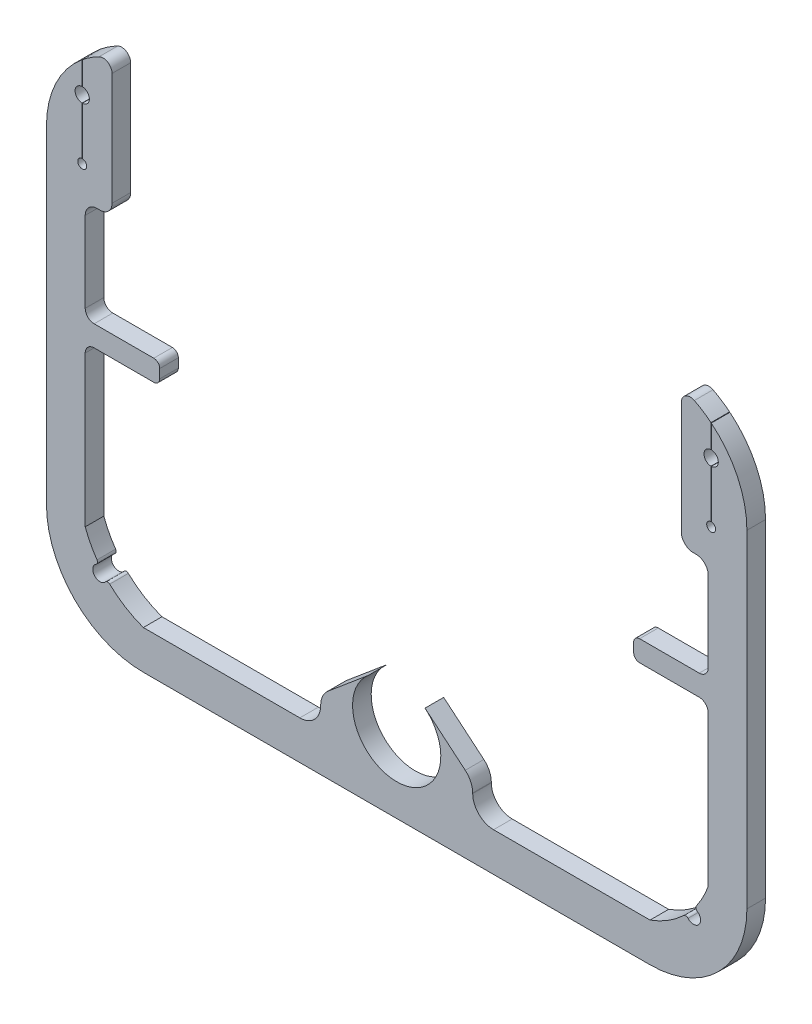
SolidWorks part; units mm, degrees
material "Delrin 2700 NC010, Low Viscosity Acetal Copolymer (SS)"
ref_plane "Front Plane" through (0, 0, 0) normal (0, 0, 1) x (1, 0, 0)
ref_plane "Top Plane" through (0, 0, 0) normal (0, 1, 0) x (1, 0, 0)
ref_plane "Right Plane" through (0, 0, 0) normal (1, 0, 0) x (0, 0, -1)
sketch "Sketch1" plane through (0, 0, 0) normal (0, 0, 1) x (1, 0, 0)
  line L0 (-21.59, -18.923) -> (-9.6321, -18.923)
  line L1 (21.59, 22.225) -> (-21.59, 22.225)
  line L2 (29.845, 13.97) -> (29.845, -13.97)
  line L3 (21.59, -22.225) -> (-21.59, -22.225)
  line L4 (-29.845, 13.97) -> (-29.845, -13.97)
  line L5 (29.845, 22.225) -> (-29.845, -22.225) construction
  line L6 (29.845, -22.225) -> (-29.845, 22.225) construction
  line L7 (9.6321, -18.923) -> (21.59, -18.923)
  line L8 (-26.543, -0.381) -> (-20.193, -0.381)
  line L9 (26.543, 1.397) -> (20.193, 1.397)
  line L10 (-26.543, 10.033) -> (-26.543, -13.97)
  line L11 (-1000, 0) -> (49000, 0) construction
  line L12 (-26.543, 0) -> (-26.543, -1.27)
  line L13 (26.543, 10.033) -> (26.543, -13.97)
  line L14 (21.59, 18.923) -> (-21.59, 18.923)
  line L15 (26.543, 1.397) -> (26.543, -0.381)
  line L16 (26.543, -0.381) -> (20.193, -0.381)
  line L17 (20.193, 1.397) -> (20.193, -0.381)
  line L18 (0, 18.923) -> (0, -18.415) construction
  line L19 (-20.193, 1.397) -> (-20.193, -0.381)
  line L20 (-26.543, 1.397) -> (-20.193, 1.397)
  line L21 (2.4164, -12.8683) -> (9.6321, -18.923)
  line L22 (-2.4164, -12.8683) -> (-9.6321, -18.923)
  line L23 (21.59, 18.923) -> (21.59, 10.033)
  line L24 (-21.59, 18.923) -> (-21.59, 10.033)
  line L26 (-21.59, 10.033) -> (-26.543, 10.033)
  line L28 (21.59, 10.033) -> (26.543, 10.033)
  line L29 (-26.543, 13.97) -> (-26.543, -13.97) construction
  line L31 (26.543, 13.97) -> (26.543, -13.97) construction
  line L36 (21.59, -18.923) -> (-21.59, -18.923) construction
  arc A0 (-2.4164, -12.8683) -> (2.4164, -12.8683) centre (0, -15.748) ccw
  arc A1 (-21.59, 22.225) -> (-29.845, 13.97) centre (-21.59, 13.97) ccw
  arc A2 (21.59, 22.225) -> (29.845, 13.97) centre (21.59, 13.97) cw
  arc A3 (29.845, -13.97) -> (21.59, -22.225) centre (21.59, -13.97) cw
  arc A4 (-21.59, -22.225) -> (-29.845, -13.97) centre (-21.59, -13.97) cw
  arc A5 (-26.543, -13.97) -> (-21.59, -18.923) centre (-18.7807, -11.1607) ccw
  arc A6 (26.543, -13.97) -> (21.59, -18.923) centre (18.7807, -11.1607) cw
  arc A13 (-21.59, -18.923) -> (-26.543, -13.97) centre (-21.59, -13.97) cw construction
  arc A14 (26.543, -13.97) -> (21.59, -18.923) centre (21.59, -13.97) cw construction
  arc A17 (21.59, 18.923) -> (26.543, 13.97) centre (21.59, 13.97) cw construction
  arc A18 (-21.59, 18.923) -> (-26.543, 13.97) centre (-21.59, 13.97) ccw construction
  point P0 (0, 0)
  dimension "D4" = 7.5184
  dimension "D6" = 8.255
  dimension "D7" = 8.255
  dimension "D8" = 8.255
  dimension "D9" = 8.255
  dimension "D5" = 8.89
  dimension "D1" = 59.69
  dimension "D2" = 44.45
  dimension "D10" = 3.302
  dimension "D3" = 3.175
  dimension "D13" = 15.748
  dimension "D14" = 1.778
  dimension "D15" = 21.844
  dimension "D16" = 6.35
extrude "Boss-Extrude1" add sketch "Sketch1" along normal blind 1.5875 contours A4 L3 A3 L2 A2 L1 A1 L4 A6 L7 L21 A0 L22 L0 A5 L10 L14 L13 | L9 L17 L16 L13 | L20 L10 L8 L19 region at (-23.368, 0.508, 0) region at (23.368, 0.508, 0) region at (26.9009, 19.2809, 0)
sketch "Sketch2" plane through (0, 0, 1.5875) normal (0, 0, 1) x (1, 0, 0)
  line L0 (-21.59, 10.033) -> (-26.543, 10.033) construction
  line L1 (-9.6321, -18.923) -> (-6.477, -18.923)
  line L2 (-9.6321, -18.923) -> (-9.6321, -16.2756)
  line L3 (-9.6321, -16.2756) -> (-6.477, -16.2756)
  line L4 (-6.477, -18.923) -> (-6.477, -16.2756)
  line L5 (0, -1000) -> (0, 49000) construction
  line L6 (9.6321, -18.923) -> (9.6321, -16.2756)
  line L7 (9.6321, -16.2756) -> (6.477, -16.2756)
  line L8 (6.477, -18.923) -> (6.477, -16.2756)
  line L9 (9.6321, -18.923) -> (6.477, -18.923)
  line L10 (-29.845, 13.97) -> (-29.845, -13.97) construction
  line L11 (-21.59, 18.923) -> (21.59, 18.923)
  line L12 (-24.257, 10.033) -> (-24.257, 22.225)
  line L13 (-24.257, 22.225) -> (24.257, 22.225)
  line L14 (24.257, 10.033) -> (24.257, 22.225)
  line L16 (21.59, 18.923) -> (-21.59, 18.923) construction
  line L17 (-2.4164, -12.8683) -> (-9.6321, -18.923) construction
  line L18 (21.59, 22.225) -> (-21.59, 22.225) construction
  line L19 (21.59, 18.923) -> (-21.59, 18.923) construction
  line L22 (-21.59, 18.923) -> (-21.59, 10.033) construction
  line L23 (21.59, 10.033) -> (26.543, 10.033) construction
  line L24 (21.59, 18.923) -> (21.59, 10.033) construction
  line L25 (-21.59, 18.923) -> (-21.59, 10.033)
  line L26 (-21.59, 10.033) -> (-24.257, 10.033)
  line L27 (21.59, 10.033) -> (24.257, 10.033)
  line L28 (21.59, 18.923) -> (21.59, 10.033)
  point P25 (0, 22.225)
  dimension "D1" = 6.477
  dimension "D2" = 5.588
extrude "Cut-Extrude1" cut sketch "Sketch2" against normal up to next
fillet "Fillet1" radius 1.778 4 edges at (6.477, -18.923, 0.7937) (6.477, -16.2756, 0.7937) (-6.477, -18.923, 0.7937) (-6.477, -16.2756, 0.7937)
fillet "Fillet2" radius 0.762 2 edges at (24.257, 21.7823, 0.7937) (-24.257, 21.7823, 0.7937)
fillet "Fillet3" radius 0.762 4 edges at (-26.543, -0.381, 0.7937) (26.543, -0.381, 0.7937) (26.543, 1.397, 0.7937) (-26.543, 1.397, 0.7937)
sketch "Sketch3" plane through (0, 0, 1.5875) normal (0, 0, 1) x (1, 0, 0)
  line L0 (-25.019, -16.51) -> (-25.2884, -16.7794) construction
  line L1 (21.59, -22.225) -> (-21.59, -22.225) construction
  line L3 (25.2884, -16.7794) -> (25.019, -16.51) construction
  circle A0 centre (-25.019, -16.51) radius 0.6096 construction
  circle A1 centre (-25.019, 16.256) radius 0.6096 construction
  circle A2 centre (25.019, 16.256) radius 0.6096 construction
  circle A3 centre (25.019, -16.51) radius 0.6096 construction
  circle A4 centre (-25.019, -16.51) radius 0.6096 construction
  circle A5 centre (-25.019, 16.256) radius 0.6096 construction
  circle A6 centre (25.019, 16.256) radius 0.6096 construction
  circle A7 centre (25.019, -16.51) radius 0.6096 construction
  circle A8 centre (-26.797, 17.78) radius 0.6096
  circle A9 centre (-25.2884, -16.7794) radius 0.6096
  circle A10 centre (26.797, 17.78) radius 0.6096
  circle A11 centre (25.2884, -16.7794) radius 0.6096
  dimension "D1" = 1.524
  dimension "D2" = 1.778
  dimension "D3" = 135
  dimension "D4" = 0.381
  dimension "D5" = 1.778
  dimension "D6" = 135
extrude "Cut-Extrude2" cut sketch "Sketch3" against normal up to surface (1.5875 mm away) up to face at (0, -3.8392, 0)
sketch "Sketch5" plane through (0, 0, 1.5875) normal (0, 0, 1) x (1, 0, 0)
  line L0 (-26.797, 19.7924) -> (-26.797, 9.1554) construction
  line L1 (-26.8097, 20.3859) -> (-26.7843, 20.3859)
  line L2 (-26.8097, 20.3859) -> (-26.8097, 13.0808)
  line L3 (-26.7843, 20.3859) -> (-26.7843, 13.0808)
  line L4 (-26.797, 17.78) -> (-26.797, 17.1704) construction
  arc A0 (-26.8097, 13.0808) -> (-26.7843, 13.0808) centre (-26.797, 12.7) ccw
  circle A1 centre (-26.797, 17.78) radius 0.6096 construction
  arc A2 (-25.3677, 21.3099) -> (-29.845, 13.97) centre (-21.59, 13.97) ccw construction
  dimension "D2" = 0.762
  dimension "D3" = 5.08
  dimension "D1" = 0.0254
extrude "Cut-Extrude3" cut sketch "Sketch5" against normal through all
fillet "Fillet4" radius 1.016 4 edges at (-26.543, 10.033, 0.7937) (26.543, 10.033, 0.7937) (24.257, 10.033, 0.7937) (-24.257, 10.033, 0.7937)
mirror "Mirror1" about plane through (0, 0, 0) normal (1, 0, 0) of "Cut-Extrude3"
fillet "Fillet5" radius 0.508 4 edges at (20.193, -0.381, 0.7937) (20.193, 1.397, 0.7937) (-20.193, -0.381, 0.7937) (-20.193, 1.397, 0.7937)
fillet "Fillet7" radius 0.254 4 edges at (25.3406, -16.172, 0.7937) (24.6951, -16.9196, 0.7937) (-24.6951, -16.9196, 0.7937) (-25.3406, -16.172, 0.7937)
equation "\"SnapInRodSlotSize\"= .02"
